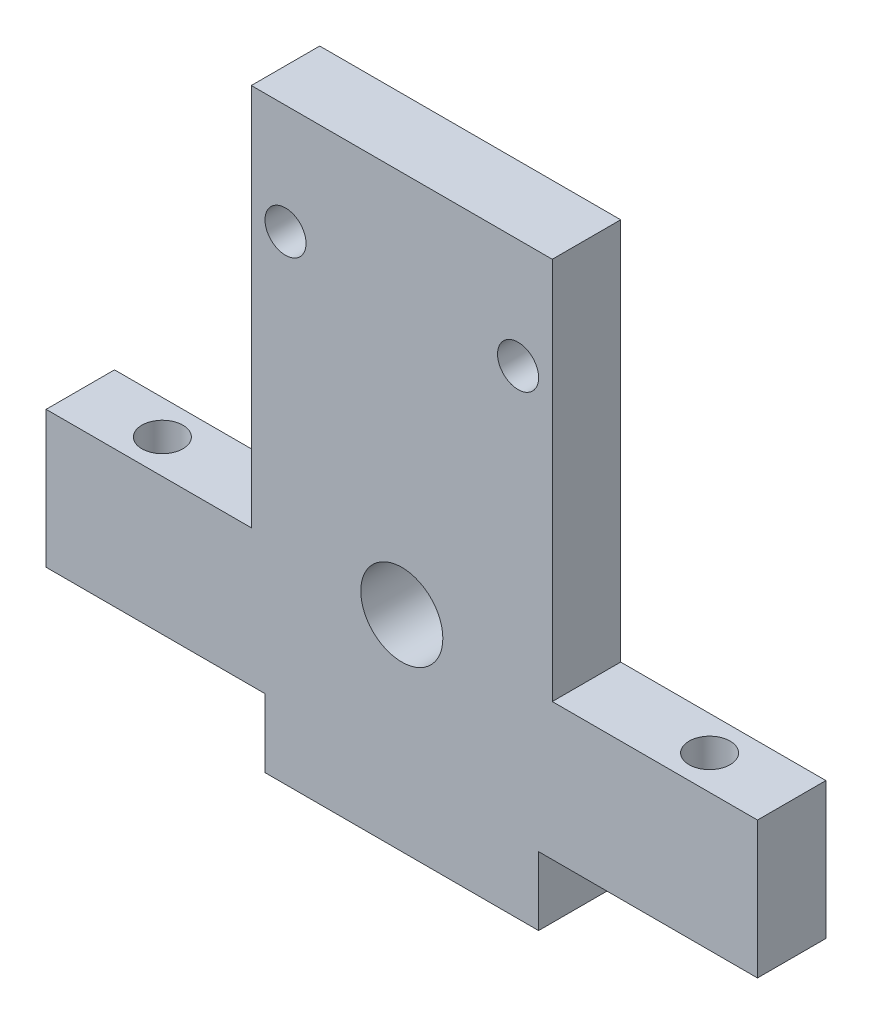
SolidWorks part; units mm, degrees
ref_plane "Front Plane" through (0, 0, 0) normal (0, 0, 1) x (1, 0, 0)
ref_plane "Top Plane" through (0, 0, 0) normal (0, 1, 0) x (1, 0, 0)
ref_plane "Right Plane" through (0, 0, 0) normal (1, 0, 0) x (0, 0, -1)
sketch "Sketch1" plane through (0, 0, 0) normal (0, 0, 1) x (1, 0, 0)
  line L0 (1.0839, 21.8298) -> (1.0839, -16.1702) construction
  line L1 (12.0839, -6.1702) -> (12.0839, 21.8298)
  line L2 (-9.9161, -6.1702) -> (-9.9161, 21.8298)
  line L3 (-9.9161, 21.8298) -> (12.0839, 21.8298)
  line L4 (-9.9161, -6.1702) -> (-24.9161, -6.1702)
  line L5 (-24.9161, -6.1702) -> (-24.9161, -16.1702)
  line L6 (-24.9161, -16.1702) -> (-8.9161, -16.1702)
  line L7 (27.0839, -6.1702) -> (27.0839, -16.1702)
  line L8 (12.0839, -6.1702) -> (27.0839, -6.1702)
  line L9 (-8.9161, -16.1702) -> (-8.9161, -21.1702)
  line L10 (-8.9161, -21.1702) -> (11.0839, -21.1702)
  line L11 (11.0839, -21.1702) -> (11.0839, -16.1702)
  line L12 (11.0839, -16.1702) -> (27.0839, -16.1702)
  circle A0 centre (1.0839, -6.1702) radius 3
  circle A1 centre (-7.4161, 13.8298) radius 1.5
  circle A2 centre (9.5839, 13.8298) radius 1.5
  point P18 (0, 0)
  point P21 (0, 0)
  dimension "D3" = 10
  dimension "D9" = 6
  dimension "D1" = 22
  dimension "D2" = 2.5
  dimension "D4" = 38
  dimension "D5" = 15
  dimension "D6" = 5
  dimension "D7" = 20
  dimension "D8" = 10
  dimension "D10" = 30
extrude "Boss-Extrude1" add sketch "Sketch1" along normal blind 5
sketch "Sketch2" plane through (0, -6.1702, 0) normal (0, 1, 0) x (1, 0, 0)
  line L1 (1.0839, 0) -> (1.0839, -5) construction
  line L2 (12.0839, 0) -> (-9.9161, 0) construction
  line L3 (12.0839, -5) -> (-9.9161, -5) construction
  circle A0 centre (-18.9161, -2.5) radius 1.5
  circle A1 centre (21.0839, -2.5) radius 1.5
  dimension "D1" = 2.5
  dimension "D2" = 40
extrude "Cut-Extrude1" cut sketch "Sketch2" against normal blind 10 contours A0
extrude "Cut-Extrude2" cut sketch "Sketch2<3>" against normal blind 10
sketch "Sketch2<3>" plane through (0, -6.1702, 0) normal (0, 1, 0) x (1, 0, 0) same geometry as "Sketch2"
